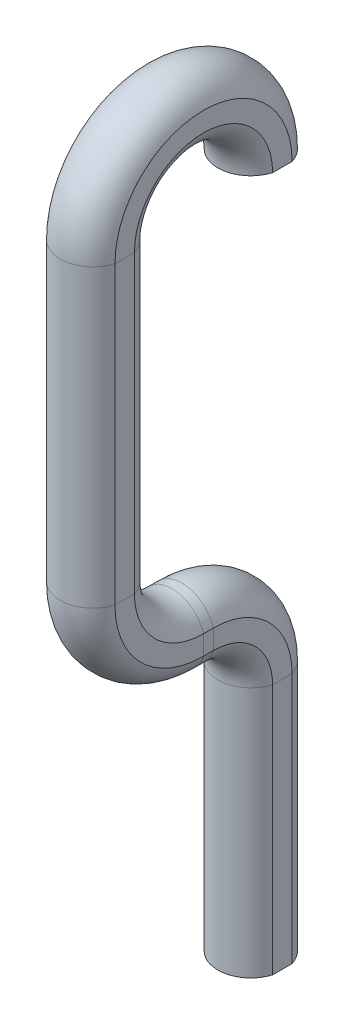
SolidWorks part; units mm, degrees
ref_plane "Front Plane" through (0, 0, 0) normal (1, 0, 0) x (0, 1, 0)
ref_plane "Top Plane" through (0, 0, 0) normal (0, 0, 1) x (0, 1, 0)
ref_plane "Right Plane" through (0, 0, 0) normal (0, 1, 0) x (-1, 0, 0)
sketch "Sketch1" plane through (0, 0, 0) normal (1, 0, 0) x (0, 1, 0)
  line L0 (0, 0) -> (64.77, 0)
  line L1 (82.55, 17.78) -> (82.55, 20.32)
  line L2 (102.87, 40.64) -> (179.07, 40.64)
  arc A0 (64.77, 0) -> (82.55, 17.78) centre (64.77, 17.78) ccw
  arc A1 (82.55, 20.32) -> (102.87, 40.64) centre (102.87, 20.32) cw
  arc A2 (179.07, 40.64) -> (179.07, 0) centre (179.07, 20.32) cw
  point P11 (0, 0)
  dimension "D1" = 20.32
  dimension "D3" = 17.78
  dimension "D4" = 20.32
  dimension "D2" = 82.55
  dimension "D5" = 40.64
  dimension "D6" = 76.2
sketch "Sketch2" plane through (0, 0, 0) normal (0, 1, 0) x (-1, 0, 0)
  line L0 (-8.128, 2.5146) -> (-8.128, -2.5146)
  line L1 (0, 17.78) -> (0, 0) construction
  line L2 (0, 17.78) -> (0, 0) construction
  line L3 (8.128, 2.5146) -> (8.128, -2.5146)
  line L4 (-8.128, 0) -> (0, 0) construction
  arc A1 (8.128, 2.5146) -> (-8.128, 2.5146) centre (0, -0.0031) ccw
  arc A2 (8.128, -2.5146) -> (-8.128, -2.5146) centre (0, 0.0031) cw
  point P9 (-7.9262, 2.5146)
  dimension "D2" = 16.256
  dimension "D3" = 8.509
  dimension "D1" = 5.0292
sweep "Sweep1" add profiles "Sketch2" path "Sketch1"
